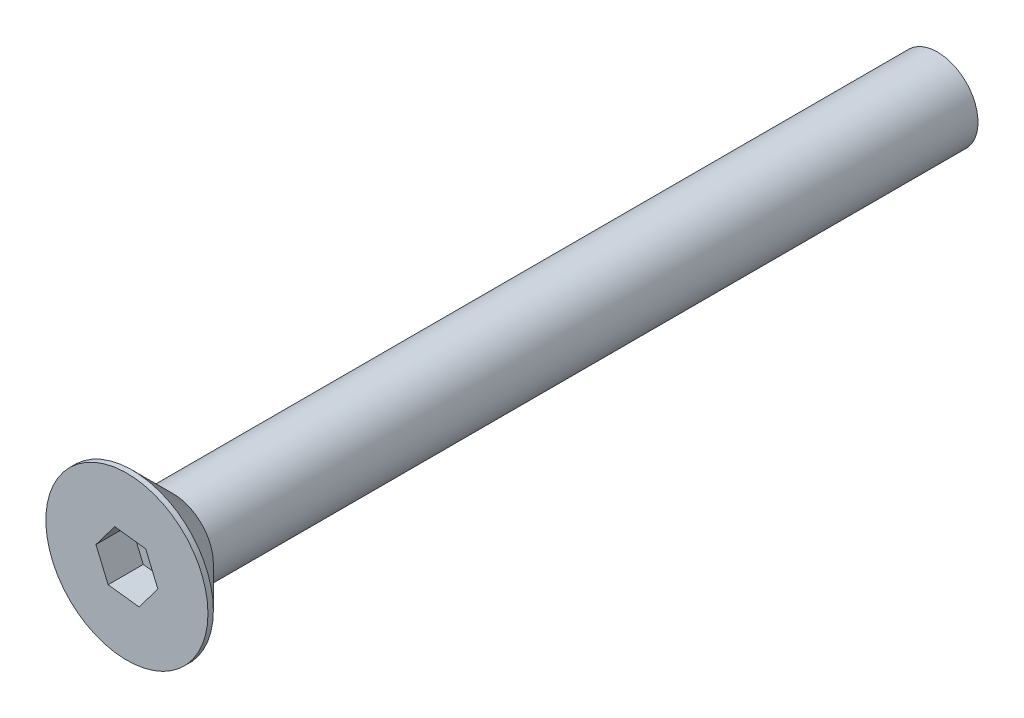
SolidWorks part; units mm, degrees
ref_plane "Front Plane" through (0, 0, 0) normal (0, 0, 1) x (1, 0, 0)
ref_plane "Top Plane" through (0, 0, 0) normal (0, 1, 0) x (1, 0, 0)
ref_plane "Right Plane" through (0, 0, 0) normal (1, 0, 0) x (0, 0, -1)
sketch "Sketch1" plane through (0, 0, 0) normal (0, 0, 1) x (1, 0, 0)
  circle A0 centre (0, 0) radius 1.5
  dimension "D1" = 3
extrude "Boss-Extrude1" add sketch "Sketch1" along normal blind 28.3
sketch "Sketch2" plane through (0, 0, 28.3) normal (0, 0, 1) x (1, 0, 0)
  circle A0 centre (0, 0) radius 3
  dimension "D1" = 6
extrude "Boss-Extrude2" add sketch "Sketch2" along normal blind 1.7
chamfer "Chamfer1" distance 1.5 angle 45 1 edges at (3, 0, 28.3)
sketch "Sketch7" plane through (0, 0, 30) normal (0, 0, 1) x (1, 0, 0)
  line L1 (0.4513, -1.0629) -> (1.1461, -0.1406)
  line L2 (1.1461, -0.1406) -> (0.6948, 0.9222)
  line L3 (0.6948, 0.9222) -> (-0.4513, 1.0629)
  line L4 (-0.4513, 1.0629) -> (-1.1461, 0.1406)
  line L5 (-1.1461, 0.1406) -> (-0.6948, -0.9222)
  line L6 (-0.6948, -0.9222) -> (0.4513, -1.0629)
  circle A0 centre (0, 0) radius 1 construction
  dimension "D1" = 2
extrude "Cut-Extrude1" cut sketch "Sketch7" against normal blind 1.3
